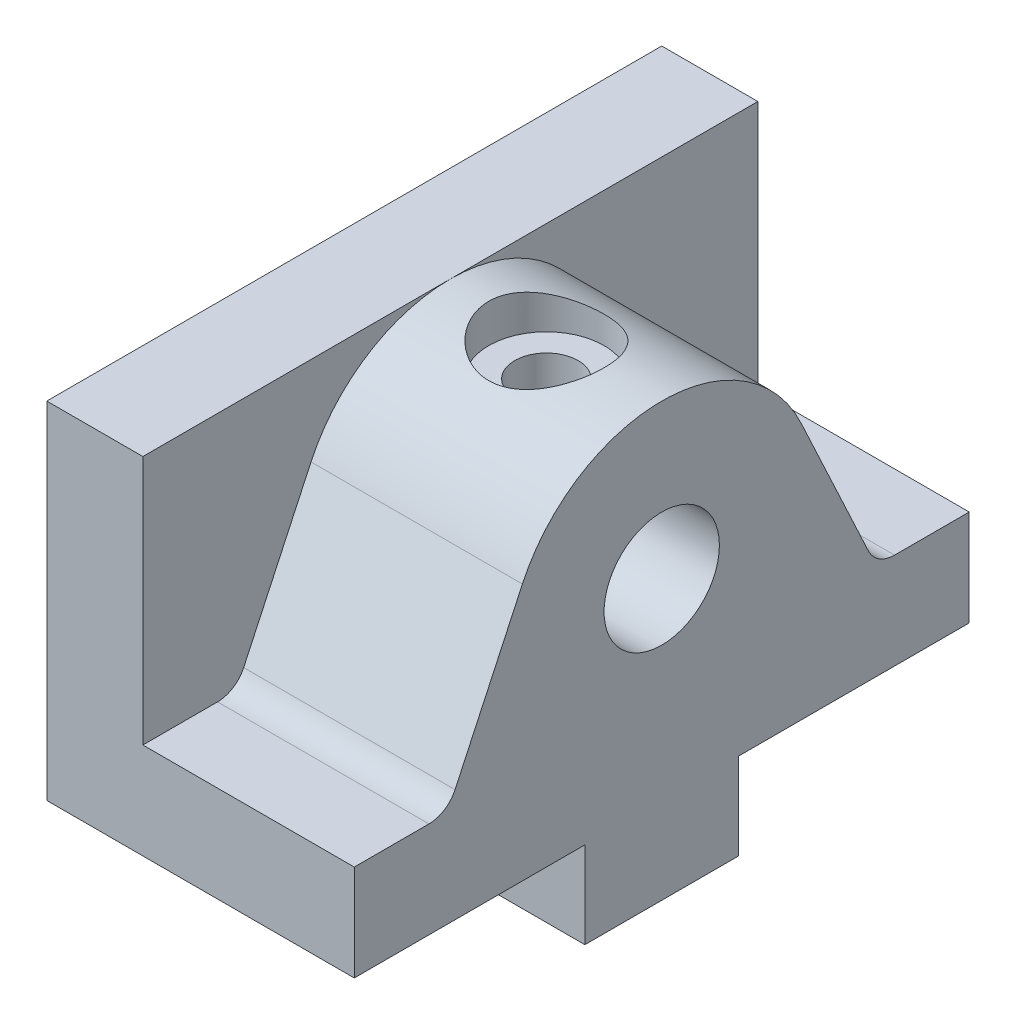
SolidWorks part; units mm, degrees
ref_plane "Front Plane" through (0, 0, 0) normal (0, 0, 1) x (1, 0, 0)
ref_plane "Top Plane" through (0, 0, 0) normal (0, 1, 0) x (1, 0, 0)
ref_plane "Right Plane" through (0, 0, 0) normal (1, 0, 0) x (0, 0, -1)
sketch "Sketch1" plane through (0, 0, 0) normal (1, 0, 0) x (0, 0, -1)
  line L0 (0, 0) -> (0, 27213.6811) construction
  line L1 (0, 0) -> (27213.6811, 0) construction
  line L2 (-32, -8) -> (32, -8)
  line L3 (-32, -18) -> (32, -18)
  line L4 (-32, -18) -> (-32, 18)
  line L5 (-32, 18) -> (32, 18)
  line L6 (32, -18) -> (32, 18)
  line L7 (-32, -18) -> (32, 18) construction
  line L8 (-32, 18) -> (32, -18) construction
  line L9 (-8, -18) -> (8, -18)
  line L10 (-8, -18) -> (-8, -27)
  line L11 (-8, -27) -> (8, -27)
  line L12 (8, -18) -> (8, -27)
  line L13 (-22.3171, -8) -> (-14.5009, 8.7619)
  line L14 (14.5009, 8.7619) -> (22.3171, -8)
  arc A0 (-14.5009, 8.7619) -> (14.5009, 8.7619) centre (0, 2) cw
  circle A1 centre (0, 2) radius 6
  point P5 (0, 0)
  dimension "D6" = 50
  dimension "D7" = 16
  dimension "D8" = 12
  dimension "D1" = 64
  dimension "D2" = 36
  dimension "D3" = 16
  dimension "D4" = 9
  dimension "D5" = 10
extrude "Boss-Extrude1" add sketch "Sketch1" along normal blind 32 contours L3 L6 L2 L4 | L12 L3 L10 L11 | A0 L13 L2 L14 A1 | A1 region at (0, -13, 0) region at (0, 0.1626, 17.9409) region at (0, -22.5, 0) region at (0, 2, 0)
extrude "Boss-Extrude2" add sketch "Sketch1<3>" along normal blind 10 contours L13 A0 L5 L4 L2 | L5 A0 L14 L2 L6 region at (0, 7.0608, 23.1196) region at (0, 7.0608, -23.1196)
sketch "Sketch1<3>" plane through (0, 0, 0) normal (1, 0, 0) x (0, 0, -1) same geometry as "Sketch1"
extrude "Cut-Extrude1" cut sketch "Sketch1<4>" against normal blind 24 from offset 32 contours A1 region at (0, 2, 0)
sketch "Sketch1<4>" plane through (0, 0, 0) normal (1, 0, 0) x (0, 0, -1) same geometry as "Sketch1"
fillet "Fillet1" radius 3 2 edges at (21, -8, -22.3171) (21, -8, 22.3171)
hole_wizard "CBORE for M6 Hex Head Bolt1" positions "Sketch3" profile "Sketch5" counterbore size "M6" standard "ANSI Metric" end condition up to next
sketch "Sketch3" plane through (0, 18, 0) normal (0, 1, 0) x (1, 0, 0)
  line L0 (0, -32) -> (0, 32) construction
  point P0 (20, 0)
  point P3 (0, 0)
  dimension "D1" = 20
sketch "Sketch5" plane through (20, 18, 0) normal (1, 0, 0) x (0, 0, 1)
  line L0 (0, 0) -> (0, 10)
  line L1 (0, 10) -> (3.3, 10)
  line L3 (3.3, 10) -> (3.3, 4)
  line L4 (3.3, 4) -> (6, 4)
  line L5 (6, 4) -> (6, 0)
  line L7 (6, 0) -> (0, 0)
  line L11 (0, -6.35) -> (0, 107.95) construction
  dimension "Thru Hole Dia." = 6.6
  dimension "Thru Hole Depth" = 10
  dimension "C'Bore Dia." = 12
  dimension "C'Bore Depth" = 4
hole_wizard "M6x1.0 Tapped Hole1" positions "Sketch6" profile "Sketch8" tap size "M6x1.0" standard "ANSI Metric"
sketch "Sketch6" plane through (0, -27, 0) normal (0, -1, 0) x (-1, 0, 0)
  line L1 (-32, -8) -> (-32, 8) construction
  point P0 (-24, 0)
  point P2 (-8, 0)
  point P4 (0, 0)
  point P10 (-32, -1.2482)
  point P13 (0, 0)
  point P14 (0, 0)
  dimension "D1" = 16
  dimension "D2" = 8
sketch "Sketch8" plane through (24, -27, 0) normal (1, 0, 0) x (0, 0, -1)
  line L0 (0, 0) -> (0, 17.5022)
  line L1 (0, 17.5022) -> (2.5, 16)
  line L2 (2.5, 16) -> (2.5, 0)
  line L5 (2.5, 0) -> (0, 0)
  line L10 (0, 17.5022) -> (-2.5, 16) construction
  line L11 (0, -6.35) -> (0, 107.95) construction
  dimension "Tap Drill Dia." = 5
  dimension "Tap Drill Depth" = 16
  dimension "Drill Angle" = 118
